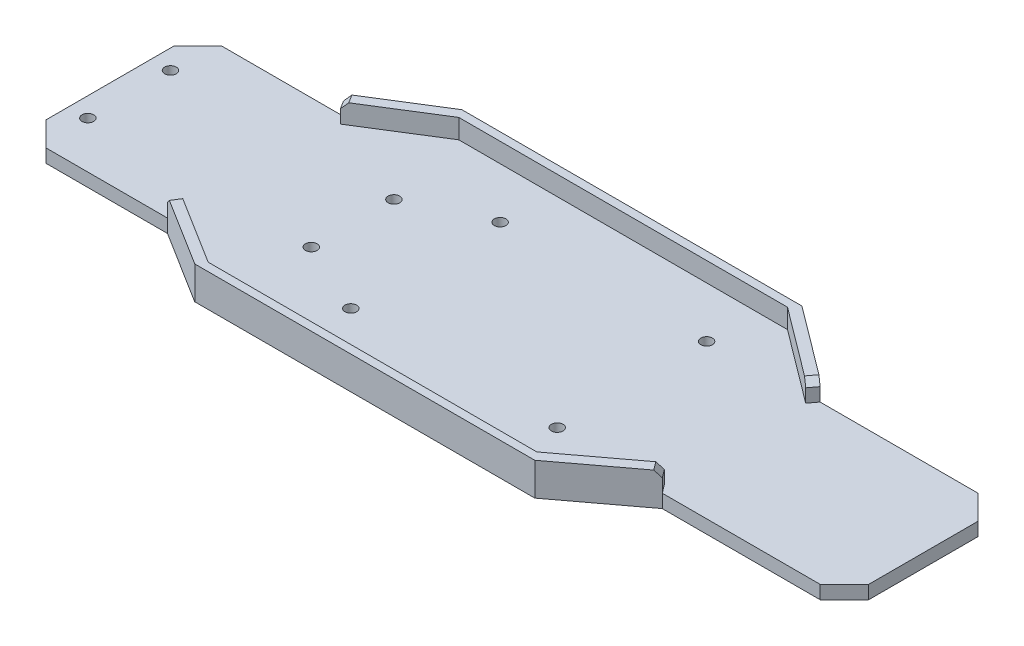
SolidWorks part; units mm, degrees
material "PETG - Polymaker"
ref_plane "Front Plane" through (0, 0, 0) normal (0, 0, 1) x (1, 0, 0)
ref_plane "Top Plane" through (0, 0, 0) normal (0, 1, 0) x (1, 0, 0)
ref_plane "Right Plane" through (0, 0, 0) normal (1, 0, 0) x (0, 0, -1)
sketch "Sketch1" plane through (0, 0, 0) normal (0, 1, 0) x (1, 0, 0)
  line L0 (-235.1499, 0) -> (235.1499, 0) construction
  line L1 (0, 0) -> (0, 52596.8311) construction
  line L2 (-100, 36.25) -> (-70, 55)
  line L3 (-70, 55) -> (70, 55)
  line L4 (-100, 36.25) -> (-160, 36.25)
  line L5 (-160, 36.25) -> (-160, -36.25)
  line L6 (-70, -55) -> (70, -55)
  line L7 (-100, -36.25) -> (-70, -55)
  line L8 (-100, -36.25) -> (-160, -36.25)
  line L9 (70, 55) -> (100, 32.5)
  line L10 (100, 32.5) -> (175, 32.5)
  line L11 (175, 32.5) -> (175, -32.5)
  line L12 (100, -32.5) -> (175, -32.5)
  line L13 (70, -55) -> (100, -32.5)
  point P3 (0, 0)
  point P10 (-85, 45.625)
  point P15 (-85, -45.625)
  point P18 (-160, 0)
  point P19 (0, -55)
  point P20 (0, 55)
  point P23 (175, 0)
  dimension "D1" = 55
  dimension "D2" = 72.5
  dimension "D3" = 30
  dimension "D4" = 60
  dimension "D5" = 140
  dimension "D6" = 75
  dimension "D7" = 65
  dimension "D8" = 30
  dimension "D9" = 110
extrude "Boss-Extrude1" add sketch "Sketch1" along normal blind 5.5
sketch "Sketch3" plane through (0, 5.5, 0) normal (0, 1, 0) x (1, 0, 0)
  line L0 (0, 0) -> (50000, 0) construction
  line L1 (0, 0) -> (0, 50000) construction
  line L2 (0, 55) -> (-70, 55)
  line L3 (70, 55) -> (-70, 55) construction
  line L4 (-70, 55) -> (-100, 36.25)
  line L5 (-100, 36.25) -> (-97.88, 32.858)
  line L6 (-97.88, 32.858) -> (-67.88, 51.608)
  line L7 (-67.88, 51.608) -> (0, 51.608)
  line L8 (-70, 55) -> (-67.88, 51.608) construction
  line L9 (0, 55) -> (70, 55)
  line L10 (70, 55) -> (100, 32.5)
  line L11 (100, 32.5) -> (97.456, 29.108)
  line L12 (97.456, 29.108) -> (67.456, 51.608)
  line L13 (67.456, 51.608) -> (0, 51.608)
  line L14 (67.456, 51.608) -> (70, 55) construction
  line L15 (67.456, -51.608) -> (70, -55) construction
  line L16 (-70, -55) -> (-67.88, -51.608) construction
  line L17 (67.456, -51.608) -> (0, -51.608)
  line L18 (97.456, -29.108) -> (67.456, -51.608)
  line L19 (100, -32.5) -> (97.456, -29.108)
  line L20 (70, -55) -> (100, -32.5)
  line L21 (0, -55) -> (70, -55)
  line L22 (-67.88, -51.608) -> (0, -51.608)
  line L23 (-97.88, -32.858) -> (-67.88, -51.608)
  line L24 (-100, -36.25) -> (-97.88, -32.858)
  line L25 (-70, -55) -> (-100, -36.25)
  line L26 (0, -55) -> (-70, -55)
  dimension "D1" = 4
extrude "Chassis-Walls1" add sketch "Sketch3" along normal blind 8
chamfer "Chamfer1" distance 10 angle 45 2 edges at (-160, 2.75, -36.25) (-160, 2.75, 36.25)
chamfer "Chamfer2" distance 10 angle 45 2 edges at (175, 2.75, -32.5) (175, 2.75, 32.5)
chamfer "Chamfer3" distance 2.5 angle 45 4 edges at (-98.94, 13.5, -34.554) (-98.94, 13.5, 34.554) (98.728, 13.5, 30.804) (98.728, 13.5, -30.804)
sketch "Sketch4" plane through (0, 0, 0) normal (0, -1, 0) x (1, 0, 0)
  line L0 (0, 0) -> (50000, 0) construction
  line L1 (-152, 17) -> (-60, 17) construction
  line L2 (-160, -26.25) -> (-160, 26.25) construction
  circle A0 centre (-152, 17) radius 2.4
  circle A1 centre (-60, 17) radius 2.4
  circle A2 centre (-60, -17) radius 2.4
  circle A3 centre (-152, -17) radius 2.4
  circle A4 centre (-30, 30.75) radius 2.4
  circle A5 centre (55, 30.75) radius 2.4
  circle A6 centre (55, -30.75) radius 2.4
  circle A7 centre (-30, -30.75) radius 2.4
  point P15 (0, 0)
  point P16 (0, 0)
  dimension "D1" = 4.8
  dimension "D2" = 4.8
  dimension "D6" = 4.8
  dimension "D8" = 4.8
  dimension "D3" = 8
  dimension "D4" = 92
  dimension "D5" = 34
  dimension "D7" = 30
  dimension "D9" = 85
  dimension "D10" = 61.5
extrude "Cut-Extrude1" cut sketch "Sketch4" against normal blind 10
equation "\"D6@Sketch4\"=\"D2@Sketch4\""
equation "\"D8@Sketch4\"=\"D2@Sketch4\""
